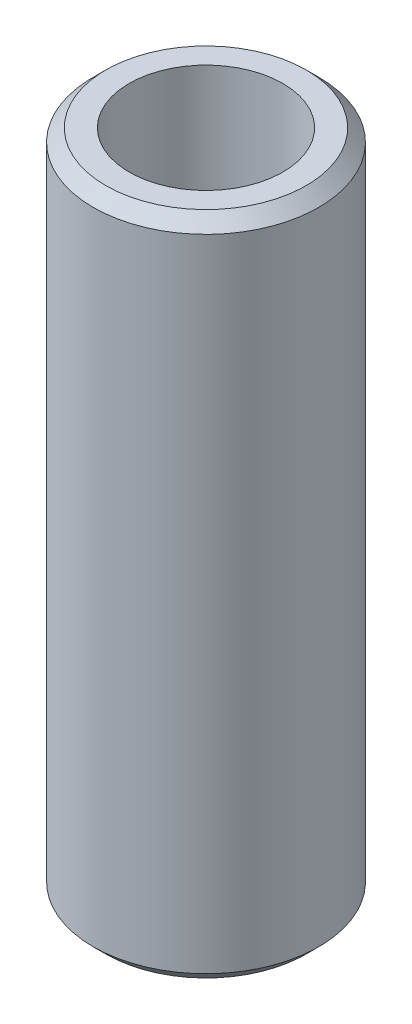
SolidWorks part; units mm, degrees
ref_plane "Front Plane" through (0, 0, 0) normal (0, 0, 1) x (1, 0, 0)
ref_plane "Top Plane" through (0, 0, 0) normal (0, 1, 0) x (1, 0, 0)
ref_plane "Right Plane" through (0, 0, 0) normal (1, 0, 0) x (0, 0, -1)
sketch "Sketch1" plane through (0, 0, 0) normal (0, 1, 0) x (1, 0, 0)
  circle A0 centre (0, 0) radius 52.5
  dimension "SHAFT_OD" = 105
extrude "Boss-Extrude1" add sketch "Sketch1" along normal blind 309.8013
sketch "Sketch2" plane through (0, 0, 0) normal (0, 1, 0) x (1, 0, 0)
  circle A0 centre (0, 0) radius 35.7661
  dimension "BORE_D" = 71.5322
extrude "Cut-Extrude1" cut sketch "Sketch2" along normal through all
chamfer "Chamfer1" distance 5.8555 angle 45 2 edges at (0, 309.8013, 52.5) (0, 0, 52.5)
